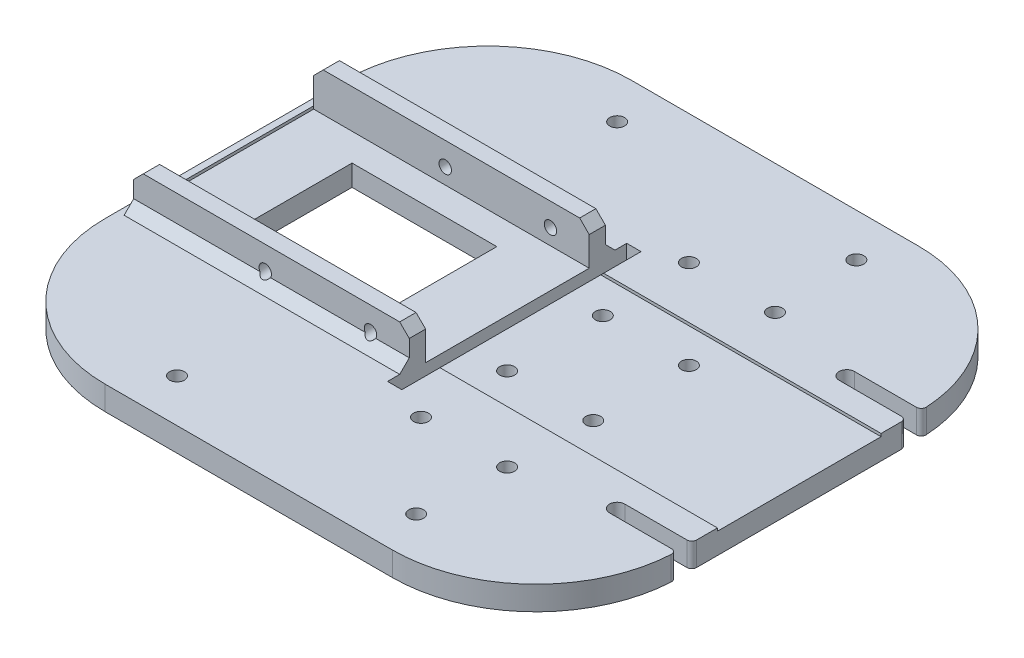
SolidWorks part; units mm, degrees
ref_plane "Front Plane" through (0, 0, 0) normal (0, 0, 1) x (1, 0, 0)
ref_plane "Top Plane" through (0, 0, 0) normal (0, 1, 0) x (1, 0, 0)
ref_plane "Right Plane" through (0, 0, 0) normal (1, 0, 0) x (0, 0, -1)
sketch "Sketch1" plane through (0, 0, 0) normal (0, 1, 0) x (1, 0, 0)
  line L1 (-60, 55) -> (60, 55)
  line L2 (-60, 55) -> (-60, -55)
  line L3 (-60, -55) -> (60, -55)
  line L4 (60, 55) -> (60, -55)
  line L5 (-60, 55) -> (60, -55) construction
  line L6 (-60, -55) -> (60, 55) construction
  line L7 (-1, 25) -> (1, 25)
  line L8 (-1, 25) -> (-1, -25)
  line L9 (-1, -25) -> (1, -25)
  line L10 (1, 25) -> (1, -25)
  line L11 (-1, 25) -> (1, -25) construction
  line L12 (-1, -25) -> (1, 25) construction
  point P0 (0, 0)
  point P6 (0, 0)
  dimension "D1" = 50
  dimension "D2" = 2
  dimension "D3" = 110
  dimension "D4" = 120
extrude "Boss-Extrude1" add sketch "Sketch1" along normal blind 5
sketch "Sketch2" plane through (0, 5, 0) normal (0, 1, 0) x (1, 0, 0)
  line L0 (-70, 0) -> (25.5144, 0) construction
  line L1 (1, -25) -> (1, 25) construction
  line L2 (9, 10) -> (27, 10) construction
  line L3 (9, 10) -> (9, 28) construction
  line L4 (9, 28) -> (27, 28) construction
  line L5 (27, 10) -> (27, 28) construction
  line L6 (-24, 46) -> (26, 46) construction
  line L7 (46, 22.4) -> (62.3911, 22.4)
  line L8 (62.3911, 22.4) -> (62.3911, 25.6)
  line L9 (62.3911, 25.6) -> (46, 25.6)
  line L10 (62.3911, -25.6) -> (46, -25.6)
  line L11 (62.3911, -22.4) -> (62.3911, -25.6)
  line L12 (46, -22.4) -> (62.3911, -22.4)
  circle A0 centre (9, 28) radius 1.55
  circle A1 centre (9, 10) radius 1.55
  circle A2 centre (27, 10) radius 1.55
  circle A3 centre (27, 28) radius 1.55
  circle A4 centre (-24, 46) radius 1.55
  circle A5 centre (26, 46) radius 1.55
  arc A8 (46, 22.4) -> (46, 25.6) centre (46, 24) cw
  arc A9 (46, 25.6) -> (47.6, 24) centre (46, 24) ccw construction
  arc A10 (46, 25.6) -> (47.6, 24) centre (46, 24) ccw construction
  arc A11 (46, -22.4) -> (46, -25.6) centre (46, -24) ccw
  circle A12 centre (27, -28) radius 1.55
  circle A13 centre (27, -10) radius 1.55
  circle A14 centre (9, -10) radius 1.55
  circle A15 centre (9, -28) radius 1.55
  circle A16 centre (26, -46) radius 1.55
  circle A17 centre (-24, -46) radius 1.55
  point P14 (1, 46)
  dimension "D1" = 3.1
  dimension "D6" = 3.1
  dimension "D8" = 50
  dimension "D2" = 10
  dimension "D3" = 18
  dimension "D4" = 18
  dimension "D5" = 8
  dimension "D7" = 46
extrude "Cut-Extrude1" cut sketch "Sketch2" against normal through all
sketch "Croquis1" plane through (0, 5, 0) normal (0, 1, 0) x (1, 0, 0)
  line L0 (-1, 25) -> (-1, -25) construction
  line L1 (-58.6, 20.55) -> (-1, 20.55)
  line L2 (-58.6, 20.55) -> (-58.6, -20.45)
  line L3 (-58.6, -20.45) -> (-1, -20.45)
  line L4 (-1, 20.55) -> (-1, -20.45)
extrude "Saliente-Extruir1" add sketch "Croquis1" along normal up to vertex (7.5 mm away)
sketch "Croquis3" plane through (-58.6, 0, 0) normal (-1, 0, 0) x (0, 0, 1)
  line L1 (17.0354, 4.4066) -> (-17.1668, 4.4066)
  line L2 (17.0354, 4.4066) -> (17.0354, 12.5)
  line L3 (17.0354, 12.5) -> (-17.1668, 12.5)
  line L4 (-17.1668, 4.4066) -> (-17.1668, 12.5)
  line L5 (-20.55, 12.5) -> (20.45, 12.5) construction
extrude "Cortar-Extruir1" cut sketch "Croquis3" against normal through all
sketch "Croquis4" plane through (0, 0, -20.55) normal (0, 0, -1) x (-1, 0, 0)
  line L0 (31.1, 42.3) -> (31.1, 28.2544) construction
  circle A0 centre (31.1, 7.7093) radius 1.3
  circle A1 centre (9.1, 7.7076) radius 1.3
  dimension "D1" = 2.6
  dimension "D2" = 22
extrude "Cortar-Extruir2" cut sketch "Croquis4" against normal through all
fillet "Redondeo1" radius 30 4 edges at (60, 2.5, -55) (-60, 2.5, -55) (60, 2.5, 55) (-60, 2.5, 55)
chamfer "Chaflán1" distance 2 angle 45 6 edges at (-58.6, 12.5, -18.8584) (-58.6, 12.5, 18.7427) (-1, 12.5, -18.8584) (-1, 12.5, 18.7427) (-29.8, 5, 20.45) (-29.8, 5, -20.55)
chamfer "Chaflán2" distance 2 angle 45 8 edges at (27, 0, -26.45) (9, 0, -26.45) (27, 0, -8.45) (9, 0, -8.45) (27, 0, 8.45) (9, 0, 8.45) (9, 0, 26.45) (27, 0, 26.45)
chamfer "Chaflán3" distance 1 angle 45 6 edges at (1, 5, -21.0834) (1, 5, 21.0177) (0, 0, 25) (-1, 0, 0) (0, 0, -25) (1, 0, 0)
fillet "Redondeo2" radius 1 4 edges at (60, 2.5, -25.6) (60, 2.5, -22.4) (60, 2.5, 22.4) (60, 2.5, 25.6)
sketch "Croquis5" plane through (0, 4.4066, 0) normal (0, 1, 0) x (1, 0, 0)
  line L2 (-44.8295, -11.4175) -> (-14.5696, -11.4175)
  line L3 (-44.8295, -11.4175) -> (-44.8295, 11.4175)
  line L4 (-44.8295, 11.4175) -> (-14.5696, 11.4175)
  line L5 (-14.5696, -11.4175) -> (-14.5696, 11.4175)
  line L6 (-44.8295, -11.4175) -> (-14.5696, 11.4175) construction
  line L7 (-44.8295, 11.4175) -> (-14.5696, -11.4175) construction
  point P2 (-29.6995, 0)
extrude "Cortar-Extruir3" cut sketch "Croquis5" against normal through all
